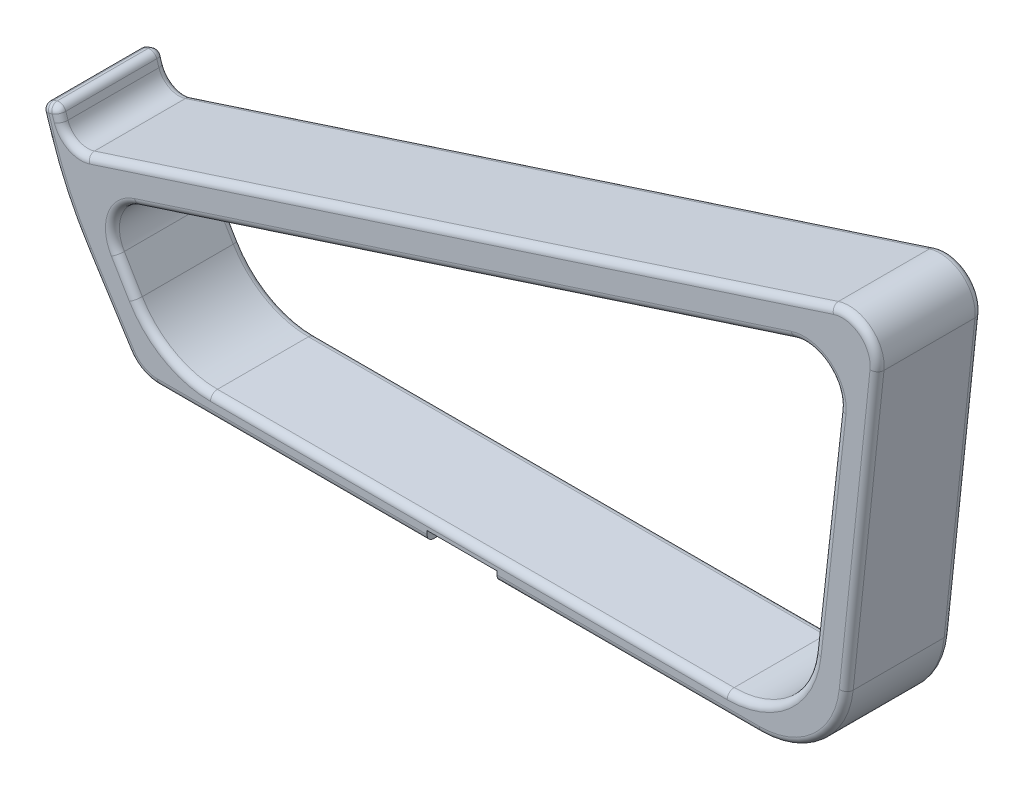
SolidWorks part; units mm, degrees
ref_plane "Front Plane" through (0, 0, 0) normal (0, 0, 1) x (1, 0, 0)
ref_plane "Top Plane" through (0, 0, 0) normal (0, 1, 0) x (1, 0, 0)
ref_plane "Right Plane" through (0, 0, 0) normal (1, 0, 0) x (0, 0, -1)
ref_axis "X Axis" through (0, 0, -132.1637) along (0, 0, 1)
ref_axis "Z Axis" through (0, -24.397, 0) along (0, 1, 0)
ref_axis "Y Axis" through (133.8141, 0, 0) along (-1, 0, 0)
ref_plane "Plane1" through (0, 0, 0) normal (-0.309, 0.9511, 0) x (0, 0, 1)
ref_plane "Plane3" through (0, 44, 0) normal (0, 1, 0) x (1, 0, 0)
sketch "Sketch1" plane through (0, 44, 0) normal (0, 1, 0) x (1, 0, 0)
  line L0 (0, -100) -> (0, 100) construction
  line L1 (0, 100) -> (-110, 100) construction
  line L2 (0, -100) -> (-110, -100) construction
  line L3 (-110, 100) -> (-110, -100) construction
  point P2 (0, 0)
  point P3 (0, 0)
  dimension "D1" = 200
  dimension "D2" = 110
ref_plane "Plane4" through (-23.4353, 72.1266, 0) normal (-0.309, 0.9511, 0) x (0.9511, 0.309, 0)
sketch "Sketch2" plane through (-23.4353, 72.1266, 0) normal (-0.309, 0.9511, 0) x (0.9511, 0.309, 0)
  line L0 (-91.0195, 115) -> (-91.0195, 85)
  line L1 (-91.0195, 115) -> (158.9805, 115)
  line L2 (158.9805, 115) -> (158.9805, 85)
  line L3 (158.9805, 85) -> (-91.0195, 85)
  point P2 (-91.0195, 100)
  dimension "D1" = 30
  dimension "D2" = 250
extrude "Boss-Extrude1" add sketch "Sketch2" against normal blind 10 contours L3 L0 L1 L2
sketch "Sketch3" plane through (-23.4353, 72.1266, 0) normal (-0.309, 0.9511, 0) x (0.9511, 0.309, 0)
  line L0 (-91.0195, 115) -> (-91.0195, 85) construction
  line L1 (-91.0195, 115) -> (-86.0195, 115)
  line L2 (-91.0195, 115) -> (-91.0195, 85)
  line L3 (-91.0195, 85) -> (-86.0195, 85)
  line L4 (-86.0195, 115) -> (-86.0195, 85)
  line L5 (158.9805, 85) -> (-91.0195, 85) construction
  dimension "D1" = 5
extrude "Boss-Extrude2" add sketch "Sketch3" along normal blind 10
sketch "Sketch4" plane through (0, 0, 0) normal (0, 1, 0) x (1, 0, 0)
  line L0 (-105.2447, 115) -> (127.7641, 115) construction
  line L1 (115, 115) -> (-85, 115)
  line L2 (115, 115) -> (115, 85)
  line L3 (115, 85) -> (-85, 85)
  line L4 (-85, 115) -> (-85, 85)
  line L5 (0, 132.1637) -> (0, -38.0933) construction
  point P7 (0, 0)
  point P8 (0, 0)
  dimension "D1" = 85
  dimension "D2" = 200
  dimension "D3" = 30
  dimension "D4" = 30
extrude "Boss-Extrude3" add sketch "Sketch4" along normal blind 6 separate body
sketch "Sketch5" plane through (0, 0, 0) normal (0, 1, 0) x (1, 0, 0)
  line L0 (-85, 85) -> (115, 85) construction
  line L1 (115, 115) -> (105, 115)
  line L2 (115, 115) -> (115, 85)
  line L3 (115, 85) -> (105, 85)
  line L4 (105, 115) -> (105, 85)
  dimension "D1" = 10
sketch "Sketch6" plane through (-23.4353, 72.1266, 0) normal (0.309, -0.9511, 0) x (0.9511, 0.309, 0)
  line L0 (158.9805, -115) -> (158.9805, -85) construction
  line L1 (158.9805, -85) -> (148.9805, -85)
  line L2 (158.9805, -85) -> (158.9805, -115)
  line L3 (158.9805, -115) -> (148.9805, -115)
  line L4 (148.9805, -85) -> (148.9805, -115)
  line L5 (-91.0195, -115) -> (158.9805, -115) construction
  dimension "D1" = 10
loft "Loft1" add profiles "Sketch6", "Sketch5" connector at (127.7641, 121.2542, -85) connector at (115, 0, -85)
sketch "Sketch9" plane through (-20.3452, 62.616, 0) normal (0.309, -0.9511, 0) x (0.9511, 0.309, 0)
  line L0 (-91.0195, -115) -> (144.4444, -115) construction
  line L1 (-91.0195, -85) -> (-81.0195, -85)
  line L2 (-91.0195, -85) -> (-91.0195, -115)
  line L3 (-91.0195, -115) -> (-81.0195, -115)
  line L4 (-81.0195, -85) -> (-81.0195, -115)
  dimension "D1" = 10
sketch "Sketch10" plane through (0, 0, 0) normal (0, 1, 0) x (1, 0, 0)
  line L0 (-85, 85) -> (105.673, 85) construction
  line L1 (-85, 115) -> (-75, 115)
  line L2 (-85, 115) -> (-85, 85)
  line L3 (-85, 85) -> (-75, 85)
  line L4 (-75, 115) -> (-75, 85)
  dimension "D1" = 10
sketch "Sketch11" plane through (113.7396, -11.9731, 0) normal (0.9945, -0.1047, 0) x (0, 0, -1)
  line L0 (85, 123.0163) -> (85, 12.0392) construction
  line L1 (85, 108) -> (115, 108)
  line L2 (85, 108) -> (85, 163)
  line L3 (85, 163) -> (115, 163)
  line L4 (115, 108) -> (115, 163)
  line L5 (115, 123.0163) -> (115, 12.0392) construction
  point P6 (115, 108)
extrude "Cut-Extrude2" cut sketch "Sketch11" along normal blind 10
loft "Loft2" add profiles "Sketch9", "Sketch10" connector at (-106.9098, 34.4894, -85) connector at (-85, 0, -85)
fillet "Fillet1" radius 25 2 edges at (105.673, 6, -100) (-78.5763, 6, -100)
fillet "Fillet9" radius 10 1 edges at (127.7641, 121.2542, -100)
fillet "Fillet8" radius 10 3 edges at (117.0296, 107.2518, -100)
fillet "Fillet11" radius 25 1 edges
fillet "Fillet5" radius 6 1 edges at (-105.2447, 45.5451, -100)
fillet "Fillet10" radius 100 1 edges at (-106.9098, 34.4894, -100)
fillet "Fillet6" radius 2 42 edges at (9.4734, 6, -115) (9.4734, 6, -85) (-76.7226, 9.263, -85) (-76.7226, 9.263, -115) (99.9836, 12.3631, -85) (99.9836, 12.3631, -115) (122.5006, 114.7553, -85) (122.5006, 114.7553, -115) (-84.321, 1.2358, -85) (-84.321, 1.2358, -115) (-91.7566, 35.4585, -85) (-91.7566, 35.4585, -115) (111.6826, 100.6957, -115) (111.6826, 100.6957, -85) (-107.7169, 53.1535, -85) (-107.7169, 53.1535, -115) (-113.0902, 53.5106, -100) (-110.7125, 54.2831, -85) (-108.3349, 55.0557, -100) (109.2203, 6.42, -115) (-110.7125, 54.2831, -115) (109.2203, 6.42, -85) (-104.1164, 47.7595, -115) (-104.1164, 47.7595, -85) (-111.9555, 50.0184, -85) (-111.9555, 50.0184, -115) (-106.1881, 34.8293, -85) (-106.1881, 34.8293, -115)
sketch "Sketch12" plane through (0, 0, 0) normal (0, -1, 0) x (1, 0, 0)
  line L0 (-79.5054, -85) -> (92.4936, -85) construction
  line L1 (-2.5054, -85) -> (17.4946, -85)
  line L2 (-2.5054, -85) -> (-2.5054, -105)
  line L3 (-2.5054, -105) -> (17.4946, -105)
  line L4 (17.4946, -85) -> (17.4946, -105)
  line L5 (7.4946, -91.25) -> (7.4946, -85) construction
  line L6 (-2.5054, -88) -> (-79.5054, -88) construction
  line L7 (9.9946, -95) -> (17.4946, -95) construction
  line L8 (4.9946, -91.25) -> (9.9946, -91.25)
  line L9 (4.9946, -91.25) -> (4.9946, -98.75)
  line L10 (4.9946, -98.75) -> (9.9946, -98.75)
  line L11 (9.9946, -91.25) -> (9.9946, -98.75)
  line L12 (-79.5054, -87) -> (-79.5054, -113) construction
  point P19 (-79.5054, -88)
  dimension "D1" = 20
  dimension "D2" = 20
  dimension "D3" = 5
  dimension "D4" = 7.5
  dimension "D5" = 77
extrude "Cut-Extrude3" cut sketch "Sketch12" against normal blind 3
